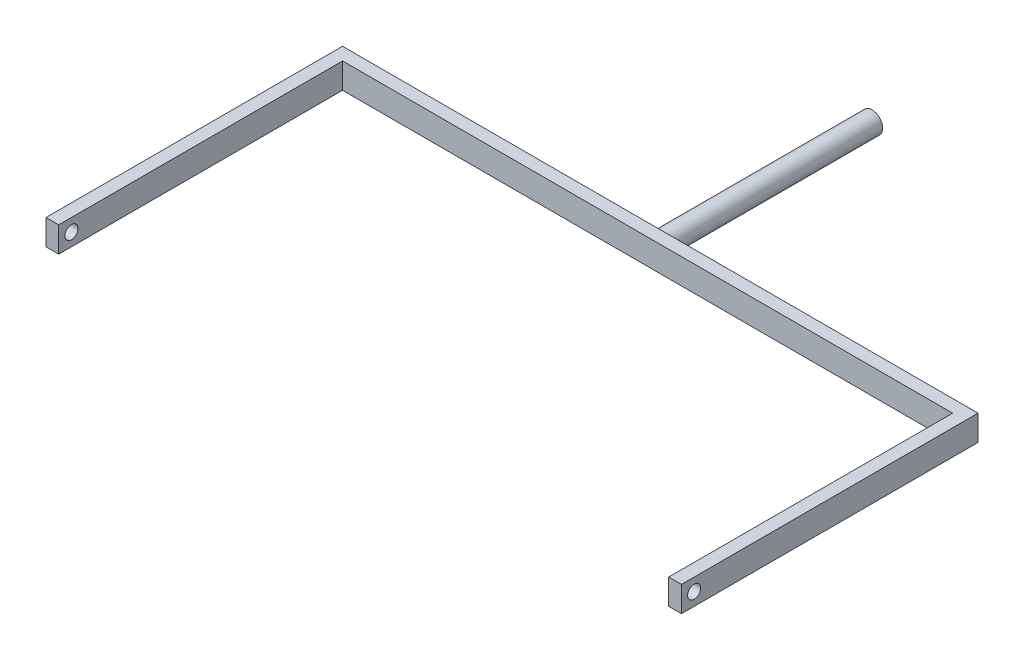
SolidWorks part; units mm, degrees
ref_plane "前视基准面" through (0, 0, 0) normal (0, 0, 1) x (1, 0, 0)
ref_plane "上视基准面" through (0, 0, 0) normal (0, 1, 0) x (1, 0, 0)
ref_plane "右视基准面" through (0, 0, 0) normal (1, 0, 0) x (0, 0, -1)
other "Configuration Table"
sketch "草图1" plane through (0, 0, 0) normal (0, 1, 0) x (1, 0, 0)
  line L0 (-72.7576, -1.4848) -> (-72.7576, -68.4848)
  line L1 (71.2424, -1.4848) -> (-72.7576, -1.4848)
  line L2 (74.2424, -1.4848) -> (74.2424, 1.5152)
  line L3 (74.2424, 1.5152) -> (-75.7576, 1.5152)
  line L4 (-75.7576, -1.4848) -> (-75.7576, 1.5152)
  line L5 (71.2424, -1.4248) -> (-75.7576, 1.5152) construction
  line L6 (74.2424, 1.5152) -> (-72.7576, -1.4848) construction
  line L7 (-75.7576, 1.5152) -> (-72.7576, 1.5152)
  line L8 (-75.7576, 1.5152) -> (-75.7576, -68.4848)
  line L9 (-75.7576, -68.4848) -> (-72.7576, -68.4848)
  line L10 (-72.7576, 1.5152) -> (-72.7576, 1.4552)
  line L11 (74.2424, 1.5152) -> (71.2424, 1.5152)
  line L12 (74.2424, 1.5152) -> (74.2424, -68.4848)
  line L13 (74.2424, -68.4848) -> (71.2424, -68.4848)
  line L14 (71.2424, 1.5152) -> (71.2424, 1.4539)
  line L15 (71.2424, -1.4248) -> (71.2424, -68.4848)
  point P0 (0, 0)
  point P12 (-72.7576, -1.4848)
  point P13 (71.2424, -1.4848)
  dimension "D1" = 150
  dimension "D2" = 3
  dimension "D3" = 3
  dimension "D4" = 70
  dimension "D5" = 70
  dimension "D6" = 3
  dimension "D7" = 67
  dimension "D8" = 67.06
  dimension "D9" = 150
  dimension "D10" = 67
extrude "凸台-拉伸2" add sketch "草图1" along normal blind 6 contours L1 L15 L13 L12 L2 L3 L4 L8 L9 L0 region at (-74.4129, 0, 34.9848)
sketch "草图2" plane through (-72.7576, 0, 0) normal (1, 0, 0) x (0, 0, -1)
  line L0 (-68.4848, 6) -> (-68.4848, 0) construction
  line L1 (-1.4848, 0) -> (-68.4848, 0) construction
  circle A0 centre (-65.4848, 3) radius 1.55
  dimension "D2" = 3.1
  dimension "D1" = 3
  dimension "D3" = 3
extrude "切除-拉伸1" cut sketch "草图2" against normal blind 10
sketch "草图3" plane through (74.2424, 0, 0) normal (1, 0, 0) x (0, 0, -1)
  line L0 (-68.4848, 6) -> (-68.4848, 0) construction
  line L1 (1.5152, 0) -> (-68.4848, 0) construction
  circle A0 centre (-65.4848, 3) radius 1.55
  dimension "D2" = 3.1
  dimension "D1" = 3
  dimension "D3" = 3
extrude "切除-拉伸2" cut sketch "草图3" against normal blind 10 contours A0
sketch "草图5" plane through (0, 0, -1.5152) normal (0, 0, -1) x (-1, 0, 0)
  line L0 (-74.2424, 0) -> (75.7576, 0) construction
  line L1 (75.7576, 6) -> (75.7576, 0) construction
  circle A0 centre (0.7576, 3) radius 2.5
  dimension "D3" = 5
  dimension "D1" = 3
  dimension "D2" = 75
extrude "凸台-拉伸3" add sketch "草图5" along normal blind 50
